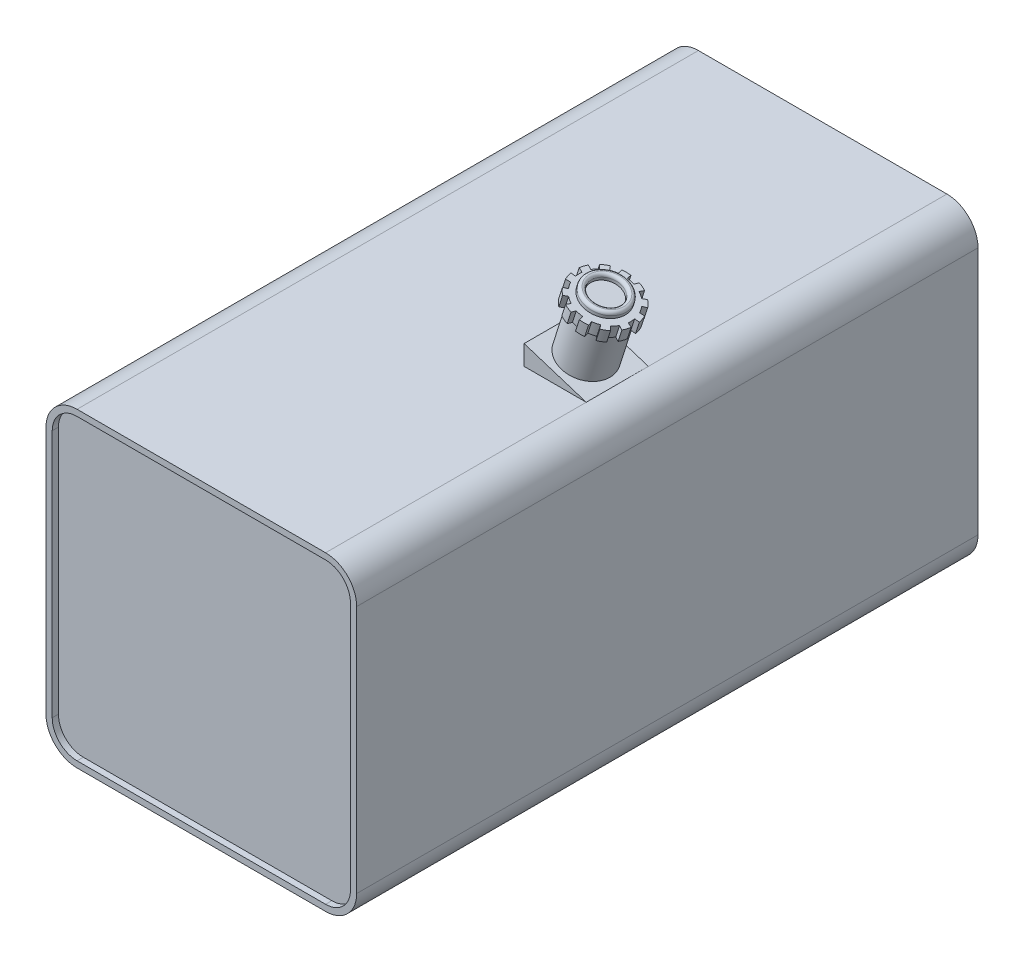
SolidWorks part; units mm, degrees
ref_plane "Front Plane" through (0, 0, 0) normal (0, 0, 1) x (1, 0, 0)
ref_plane "Top Plane" through (0, 0, 0) normal (0, 1, 0) x (1, 0, 0)
ref_plane "Right Plane" through (0, 0, 0) normal (1, 0, 0) x (0, 0, -1)
sketch "Sketch1" plane through (0, 0, 0) normal (0, 0, 1) x (1, 0, 0)
  line L1 (-20, 25) -> (20, 25)
  line L2 (-25, 20) -> (-25, -20)
  line L3 (-20, -25) -> (20, -25)
  line L4 (25, 20) -> (25, -20)
  line L5 (-25, 25) -> (25, -25) construction
  line L6 (-25, -25) -> (25, 25) construction
  arc A0 (20, -25) -> (25, -20) centre (20, -20) ccw
  arc A1 (-20, -25) -> (-25, -20) centre (-20, -20) cw
  arc A2 (25, 20) -> (20, 25) centre (20, 20) ccw
  arc A3 (-20, 25) -> (-25, 20) centre (-20, 20) ccw
  point P0 (0, 0)
  dimension "D3" = 5
  dimension "D1" = 50
  dimension "D2" = 50
extrude "Boss-Extrude1" add sketch "Sketch1" along normal blind 100
shell "Shell9" thickness 3 removed face at (0, 0, 0)
sketch "Sketch2" plane through (0, 0, 100) normal (0, 0, 1) x (1, 0, 0)
  line L8 (24, -20) -> (24, 20)
  line L9 (20, 24) -> (-20, 24)
  line L10 (-24, 20) -> (-24, -20)
  line L11 (-20, -24) -> (20, -24)
  line L12 (24, -20) -> (24, 20)
  line L13 (20, 24) -> (-20, 24)
  line L14 (-24, 20) -> (-24, -20)
  line L15 (-20, -24) -> (20, -24)
  arc A8 (20, -24) -> (24, -20) centre (20, -20) ccw
  arc A9 (24, 20) -> (20, 24) centre (20, 20) ccw
  arc A10 (-20, 24) -> (-24, 20) centre (-20, 20) ccw
  arc A11 (-24, -20) -> (-20, -24) centre (-20, -20) ccw
  arc A12 (20, -24) -> (24, -20) centre (20, -20) ccw
  arc A13 (24, 20) -> (20, 24) centre (20, 20) ccw
  arc A14 (-20, 24) -> (-24, 20) centre (-20, 20) ccw
  arc A15 (-24, -20) -> (-20, -24) centre (-20, -20) ccw
  dimension "D1" = 1
extrude "Cut-Extrude1" cut sketch "Sketch2" against normal blind 1
sketch "Sketch3" plane through (0, 0, 0) normal (0, 0, -1) x (-1, 0, 0)
  line L8 (-20, -24) -> (20, -24)
  line L9 (24, -20) -> (24, 20)
  line L10 (20, 24) -> (-20, 24)
  line L11 (-24, 20) -> (-24, -20)
  line L12 (-20, -24) -> (20, -24)
  line L13 (24, -20) -> (24, 20)
  line L14 (20, 24) -> (-20, 24)
  line L15 (-24, 20) -> (-24, -20)
  arc A8 (-24, -20) -> (-20, -24) centre (-20, -20) ccw
  arc A9 (20, -24) -> (24, -20) centre (20, -20) ccw
  arc A10 (24, 20) -> (20, 24) centre (20, 20) ccw
  arc A11 (-20, 24) -> (-24, 20) centre (-20, 20) ccw
  arc A12 (-24, -20) -> (-20, -24) centre (-20, -20) ccw
  arc A13 (20, -24) -> (24, -20) centre (20, -20) ccw
  arc A14 (24, 20) -> (20, 24) centre (20, 20) ccw
  arc A15 (-20, 24) -> (-24, 20) centre (-20, 20) ccw
  dimension "D1" = 1
extrude "Cut-Extrude2" cut sketch "Sketch3" against normal blind 1
sketch "Sketch4" plane through (0, 25, 0) normal (0, 1, 0) x (1, 0, 0)
  line L0 (20, -100) -> (20, 0) construction
  line L1 (10, -48.0496) -> (20, -48.0496)
  line L2 (10, -48.0496) -> (10, -58.0496)
  line L3 (10, -58.0496) -> (20, -58.0496)
  line L4 (20, -48.0496) -> (20, -58.0496)
  dimension "D1" = 10
  dimension "D2" = 10
extrude "Boss-Extrude2" add sketch "Sketch4" along normal blind 5
sketch "Sketch5" plane through (0, 0, 58.0496) normal (0, 0, 1) x (1, 0, 0)
  line L3 (10, 30) -> (10, 25) construction
  line L4 (10, 28.1854) -> (20, 25)
  line L5 (10, 28.1854) -> (10, 30)
  line L6 (10, 30) -> (20, 30)
  line L7 (20, 30) -> (20, 25)
extrude "Cut-Extrude5" cut sketch "Sketch5" against normal up to surface (10 mm away) up to face at (15, 27.5, 48.0496)
sketch "Sketch6" plane through (9.0724, 28.4809, 0) normal (0.3035, 0.9528, 0) x (0.9528, -0.3035, 0)
  line L4 (11.4686, -48.0496) -> (0.9736, -48.0496)
  line L5 (0.9736, -48.0496) -> (0.9736, -58.0496)
  line L6 (0.9736, -58.0496) -> (11.4686, -58.0496)
  line L7 (11.4686, -58.0496) -> (11.4686, -48.0496)
  line L8 (11.4686, -48.0496) -> (0.9736, -48.0496)
  line L9 (0.9736, -48.0496) -> (0.9736, -58.0496)
  line L10 (0.9736, -58.0496) -> (11.4686, -58.0496)
  line L11 (11.4686, -58.0496) -> (11.4686, -48.0496)
  dimension "D1" = 0
extrude "Boss-Extrude3" add sketch "Sketch6" along normal blind 10
sketch "Sketch7" plane through (12.1075, 38.0092, 0) normal (0.3035, 0.9528, 0) x (0.9528, -0.3035, 0)
  line L0 (6.2211, -48.0496) -> (6.2211, -58.0496) construction
  line L1 (11.4686, -48.0496) -> (0.9736, -48.0496) construction
  line L2 (0.9736, -58.0496) -> (11.4686, -58.0496) construction
  line L3 (0.9736, -53.0496) -> (11.4686, -53.0496) construction
  line L4 (0.9736, -48.0496) -> (0.9736, -58.0496) construction
  line L5 (11.4686, -58.0496) -> (11.4686, -48.0496) construction
  circle A0 centre (6.2211, -53.0496) radius 4
  line M3 (11.4686, -58.0496) -> (11.4686, -48.0496)
  line M4 (11.4686, -48.0496) -> (0.9736, -48.0496)
  line M5 (0.9736, -48.0496) -> (0.9736, -58.0496)
  line M6 (0.9736, -58.0496) -> (11.4686, -58.0496)
  dimension "D1" = 8
extrude "Cut-Extrude6" cut sketch "Sketch7" against normal blind 10 contours A0 M6 M3 M4 M5 region at (18.0352, 36.121, 57.9047)
sketch "Sketch8" plane through (12.1075, 38.0092, 0) normal (0.3035, 0.9528, 0) x (0.9528, -0.3035, 0)
  circle A3 centre (6.2211, -53.0496) radius 5
  circle A4 centre (6.2211, -53.0496) radius 5
  dimension "D1" = 1
extrude "Boss-Extrude4" add sketch "Sketch8" against normal blind 2
sketch "Sketch9" plane through (12.1075, 38.0092, 0) normal (0.3035, 0.9528, 0) x (0.9528, -0.3035, 0)
  line L0 (1.2211, -53.0496) -> (11.2211, -53.0496) construction
  line L1 (6.2211, -53.0496) -> (6.2211, -58.0496) construction
  line L2 (1.2878, -53.8639) -> (1.974, -53.7506)
  line L3 (1.974, -53.7506) -> (1.9322, -52.6831)
  line L4 (1.9322, -52.6831) -> (1.2519, -52.4958)
  circle A0 centre (6.2211, -53.0496) radius 5 construction
  arc A1 (1.9322, -52.6831) -> (1.974, -53.7506) centre (6.2211, -53.0496) ccw
  arc A2 (1.2519, -52.4958) -> (1.2878, -53.8639) centre (6.2211, -53.0496) ccw
  circle M3 centre (6.2211, -53.0496) radius 5
extrude "Cut-Extrude7" cut sketch "Sketch9" against normal blind 2 contours A1 L4 L2 M3 region at (13.6038, 37.5325, 53.1984)
pattern_circular "CirPattern1" count 12 over 360 about axis through (17.4281, 34.2153, 53.0496) along (0.3035, 0.9528, 0) of "Cut-Extrude7" reverse direction yes
sketch "Sketch10" plane through (12.1075, 38.0092, 0) normal (0.3035, 0.9528, 0) x (0.9528, -0.3035, 0)
  circle A0 centre (6.0559, -52.8986) radius 3.4016
  circle A1 centre (6.0559, -52.8986) radius 2.4016
  dimension "D1" = 1
extrude "Boss-Extrude5" add sketch "Sketch10" along normal blind 1
fillet "Fillet2" radius 0.5 1 edges at (14.9402, 38.1564, 52.8986)
fillet "Fillet3" radius 0.5 1 edges at (15.893, 37.8529, 52.8986)
sketch "Sketch12" plane through (0, 0, 1) normal (0, 0, -1) x (-1, 0, 0)
  line L4 (-20, -24) -> (20, -24)
  line L5 (24, -20) -> (24, 20)
  line L6 (20, 24) -> (-20, 24)
  line L7 (-24, 20) -> (-24, -20)
  line L8 (-20, -24) -> (20, -24)
  line L9 (24, -20) -> (24, 20)
  line L10 (20, 24) -> (-20, 24)
  line L11 (-24, 20) -> (-24, -20)
  arc A4 (-24, -20) -> (-20, -24) centre (-20, -20) ccw
  arc A5 (20, -24) -> (24, -20) centre (20, -20) ccw
  arc A6 (24, 20) -> (20, 24) centre (20, 20) ccw
  arc A7 (-20, 24) -> (-24, 20) centre (-20, 20) ccw
  arc A8 (-24, -20) -> (-20, -24) centre (-20, -20) ccw
  arc A9 (20, -24) -> (24, -20) centre (20, -20) ccw
  arc A10 (24, 20) -> (20, 24) centre (20, 20) ccw
  arc A11 (-20, 24) -> (-24, 20) centre (-20, 20) ccw
  dimension "D1" = 0
extrude "Cut-Extrude8" cut sketch "Sketch12" against normal blind 3
